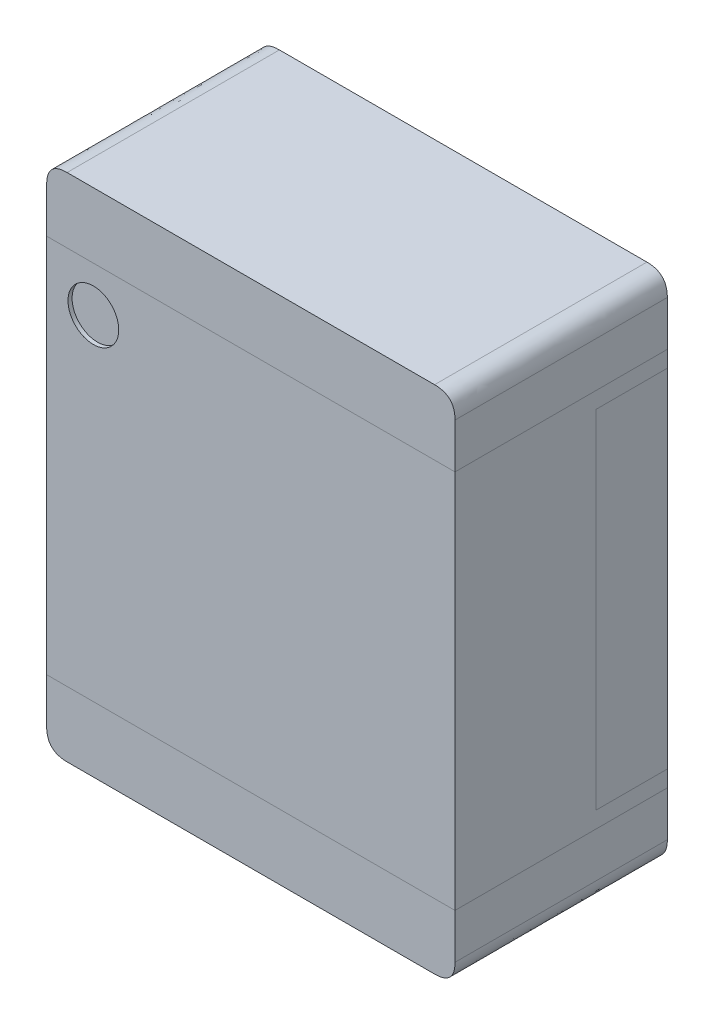
SolidWorks part; units mm, degrees
ref_plane "Front Plane" through (0, 0, 0) normal (0, 0, 1) x (1, 0, 0)
ref_plane "Top Plane" through (0, 0, 0) normal (0, 1, 0) x (1, 0, 0)
ref_plane "Right Plane" through (0, 0, 0) normal (1, 0, 0) x (0, 0, -1)
sketch "Sketch1" plane through (0, 0, 0) normal (0, 0, 1) x (1, 0, 0)
  line L1 (-1, -0.93) -> (1, -0.93)
  line L2 (-1, -0.93) -> (-1, 0.93)
  line L3 (-1, 0.93) -> (1, 0.93)
  line L4 (1, -0.93) -> (1, 0.93)
  line L5 (-1, -0.93) -> (1, 0.93) construction
  line L6 (-1, 0.93) -> (1, -0.93) construction
  point P0 (0, 0)
  dimension "D1" = 2
  dimension "D2" = 1.86
extrude "Boss-Extrude1" add sketch "Sketch1" along normal blind 1.04
sketch "Sketch8" plane through (0, 0.93, 0) normal (0, 1, 0) x (1, 0, 0)
  line L1 (-1, -1.04) -> (1, -1.04)
  line L2 (-1, -1.04) -> (-1, 0)
  line L3 (-1, 0) -> (1, 0)
  line L4 (1, -1.04) -> (1, 0)
extrude "Boss-Extrude3" add sketch "Sketch8" along normal blind 0.32 separate body
sketch "Sketch10" plane through (0, -0.93, 0) normal (0, -1, 0) x (-1, 0, 0)
  line L1 (1, 0) -> (-1, 0)
  line L2 (1, 0) -> (1, -1.04)
  line L3 (1, -1.04) -> (-1, -1.04)
  line L4 (-1, 0) -> (-1, -1.04)
extrude "Boss-Extrude4" add sketch "Sketch10" along normal blind 0.32 separate body
fillet "Fillet1" radius 0.1 2 edges at (1, 1.25, 0.52) (-1, 1.25, 0.52) conic rho 0.5
fillet "Fillet2" radius 0.1 2 edges at (1, -1.25, 0.52) (-1, -1.25, 0.52) conic rho 0.5
sketch "Sketch11" plane through (0, 0, 0) normal (0, 0, 1) x (1, 0, 0)
  line L0 (-1, 0.93) -> (-1, -0.93) construction
  line L1 (1, 0.85) -> (-1, 0.85)
  line L2 (1, 0.85) -> (1, -0.85)
  line L3 (1, -0.85) -> (-1, -0.85)
  line L4 (-1, 0.85) -> (-1, -0.85)
  line L5 (1, 0.85) -> (-1, -0.85) construction
  line L6 (1, -0.85) -> (-1, 0.85) construction
  point P0 (0, 0)
  dimension "D1" = 1.7
extrude "Cut-Extrude1" cut sketch "Sketch11" along normal blind 0.35
extrude "Boss-Extrude5" add sketch "Sketch11<2>" along normal blind 0.35 separate body
sketch "Sketch11<2>" plane through (0, 0, 0) normal (0, 0, 1) x (1, 0, 0) same geometry as "Sketch11"
sketch "Sketch13" plane through (0, 0, 0) normal (0, 0, -1) x (-1, 0, 0)
  line L0 (-0.75, 0.15) -> (-0.75, -0.15)
  line L1 (-0.55, 0.75) -> (0.4198, 0.75)
  line L2 (-0.55, 0.75) -> (-0.55, -0.75)
  line L3 (-0.55, -0.75) -> (0.55, -0.75)
  line L4 (0.55, 0.6198) -> (0.55, -0.75)
  line L5 (-0.55, 0.75) -> (0.55, -0.75) construction
  line L6 (-0.55, -0.75) -> (0.4949, 0.6749) construction
  line L7 (0.95, 0.15) -> (0.75, 0.15)
  line L8 (0.95, 0.15) -> (0.95, -0.15)
  line L9 (0.95, -0.15) -> (0.75, -0.15)
  line L10 (0.75, 0.15) -> (0.75, -0.15)
  line L11 (0.95, 0.15) -> (0.75, -0.15) construction
  line L12 (0.95, -0.15) -> (0.75, 0.15) construction
  line L13 (-0.75, 0.15) -> (-0.95, 0.15)
  line L14 (-0.95, 0.15) -> (-0.95, -0.15)
  line L15 (-0.75, -0.15) -> (-0.95, -0.15)
  line L16 (0.95, 0.7) -> (0.95, 0.4)
  line L17 (0.95, 0.7) -> (0.75, 0.7)
  line L18 (0.75, 0.7) -> (0.75, 0.4)
  line L19 (0.95, 0.4) -> (0.75, 0.4)
  line L20 (-0.75, 0.7) -> (-0.95, 0.7)
  line L21 (-0.75, 0.7) -> (-0.75, 0.4)
  line L22 (-0.75, 0.4) -> (-0.95, 0.4)
  line L23 (-0.95, 0.7) -> (-0.95, 0.4)
  line L24 (0.95, -0.4) -> (0.95, -0.7)
  line L25 (0.95, -0.4) -> (0.75, -0.4)
  line L26 (0.75, -0.4) -> (0.75, -0.7)
  line L27 (0.95, -0.7) -> (0.75, -0.7)
  line L28 (-0.75, -0.4) -> (-0.95, -0.4)
  line L29 (-0.75, -0.4) -> (-0.75, -0.7)
  line L30 (-0.75, -0.7) -> (-0.95, -0.7)
  line L31 (-0.95, -0.4) -> (-0.95, -0.7)
  line L32 (0.55, 0.6198) -> (0.4198, 0.75)
  point P0 (0, 0)
  point P6 (0.85, 0)
  dimension "D1" = 1.1
  dimension "D3" = 0.3
  dimension "D4" = 0.2
  dimension "D5" = 0.2
  dimension "D6" = 2
  dimension "D7" = 2
  dimension "D8" = 2
extrude "Boss-Extrude6" add sketch "Sketch13" along normal blind 0.02 separate body
sketch "Sketch14" plane through (0, 0, 1.04) normal (0, 0, 1) x (1, 0, 0)
  circle A0 centre (-0.7712, 0.7091) radius 0.1243
  point P2 (-0.7712, 0.7091)
extrude "Cut-Extrude2" cut sketch "Sketch14" against normal blind 0.02
